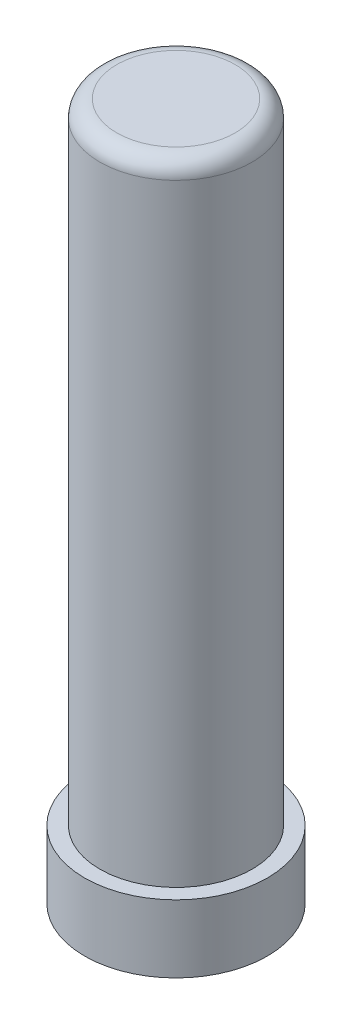
SolidWorks part; units mm, degrees
material "6061-T6 (SS)"
ref_plane "Front Plane" through (0, 0, 0) normal (0, 0, 1) x (1, 0, 0)
ref_plane "Top Plane" through (0, 0, 0) normal (0, 1, 0) x (1, 0, 0)
ref_plane "Right Plane" through (0, 0, 0) normal (1, 0, 0) x (0, 0, -1)
sketch "Sketch1" plane through (0, 0, 0) normal (0, 1, 0) x (1, 0, 0)
  line L1 (-2.8, -2.7) -> (2.8, -2.7) construction
  line L2 (-2.8, -2.7) -> (-2.8, 2.7) construction
  line L3 (-2.8, 2.7) -> (2.8, 2.7) construction
  line L4 (2.8, -2.7) -> (2.8, 2.7) construction
  line L5 (-2.8, -2.7) -> (2.8, 2.7) construction
  line L6 (-2.8, 2.7) -> (2.8, -2.7) construction
  circle A0 centre (0, 0) radius 2.7
  point P0 (0, 0)
  dimension "D1" = 5.6
  dimension "D2" = 5.4
extrude "Boss-Extrude1" add sketch "Sketch1" along normal blind 2
sketch "Sketch2" plane through (0, 2, 0) normal (0, 1, 0) x (1, 0, 0)
  circle A0 centre (0, 0) radius 2.25
  dimension "D1" = 4.5
sketch "Sketch3" plane through (0, 0, 0) normal (0, -1, 0) x (1, 0, 0)
  circle A0 centre (0, 0) radius 1.2
  circle A1 centre (0, 0) radius 0.95
  point P0 (0, 0)
  dimension "D1" = 2.4
  dimension "D2" = 1.9
extrude "Cut-Extrude2" cut sketch "Sketch3" against normal blind 9.5 contours A1
extrude "Boss-Extrude2" add sketch "Sketch2" along normal blind 18.6
sketch "Sketch7" plane through (0, 0, 0) normal (0, -1, 0) x (1, 0, 0)
  circle A0 centre (0, 0) radius 1.2
  dimension "D1" = 2.4
extrude "Cut-Extrude4" cut sketch "Sketch7" against normal blind 2.8
fillet "Fillet2" radius 0.5 1 edges at (0, 20.6, 2.25)
sketch "Sketch8" plane through (0, 0, 0) normal (0, -1, 0) x (1, 0, 0)
  circle A0 centre (0, 0) radius 0.95
  dimension "D1" = 1.9
extrude "Cut-Extrude5" cut sketch "Sketch8" against normal blind 10.5
